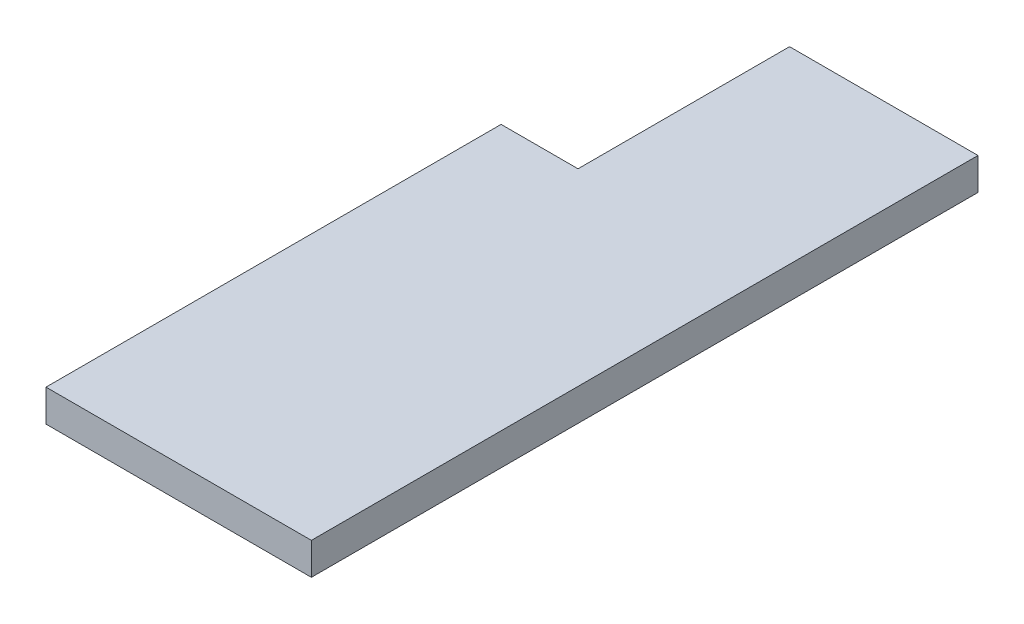
SolidWorks part; units mm, degrees
ref_plane "Front Plane" through (0, 0, 0) normal (0, 0, 1) x (1, 0, 0)
ref_plane "Top Plane" through (0, 0, 0) normal (0, 1, 0) x (1, 0, 0)
ref_plane "Right Plane" through (0, 0, 0) normal (1, 0, 0) x (0, 0, -1)
sketch "Sketch1" plane through (0, 0, 0) normal (0, 1, 0) x (1, 0, 0)
  line L1 (0, 0) -> (-53.594, 0)
  line L2 (0, 0) -> (0, 82.55)
  line L3 (0, 82.55) -> (-53.594, 82.55)
  line L4 (-53.594, 0) -> (-53.594, 82.55)
  dimension "D1" = 82.55
  dimension "D2" = 53.594
extrude "Boss-Extrude1" add sketch "Sketch1" along normal blind 6.35
sketch "Sketch6" plane through (0, 0, 0) normal (0, 0, 1) x (1, 0, 0)
  line L1 (0, 6.35) -> (-53.594, 6.35)
  line L2 (0, 6.35) -> (0, 0)
  line L3 (0, 0) -> (-53.594, 0)
  line L4 (-53.594, 6.35) -> (-53.594, 0)
extrude "Boss-Extrude3" add sketch "Sketch6" along normal blind 7.62
ref_plane "KORAL!!!" through (-26.797, 0, 0) normal (1, 0, 0) x (0, 0, -1)
sketch "Sketch3" plane through (0, 6.35, 0) normal (0, 1, 0) x (1, 0, 0)
  line L1 (0, 82.55) -> (0, -7.62)
  line L2 (-0.508, -7.62) -> (-0.508, 82.55)
  line L3 (0, 82.55) -> (-53.594, 82.55) construction
  line L4 (-0.508, 82.55) -> (0, 82.55)
  line L6 (0, -7.62) -> (-53.594, -7.62) construction
  line L7 (0, -7.62) -> (-0.508, -7.62)
  dimension "D1" = 0.508
extrude "Cut-Extrude2" cut sketch "Sketch3" against normal up to next
mirror "Mirror1" about plane through (-26.797, 0, 0) normal (1, 0, 0) of "Cut-Extrude2"
sketch "Sketch8" plane through (0, 0, -82.55) normal (0, 0, -1) x (-1, 0, 0)
  line L0 (0.508, 0) -> (53.086, 0) construction
  line L1 (0.508, 6.35) -> (37.846, 6.35)
  line L2 (0.508, 6.35) -> (0.508, 0)
  line L3 (0.508, 0) -> (37.846, 0)
  line L4 (37.846, 6.35) -> (37.846, 0)
  line L5 (53.086, 0) -> (53.086, 6.35) construction
  dimension "D1" = 15.24
extrude "Boss-Extrude4" add sketch "Sketch8" along normal blind 41.91
